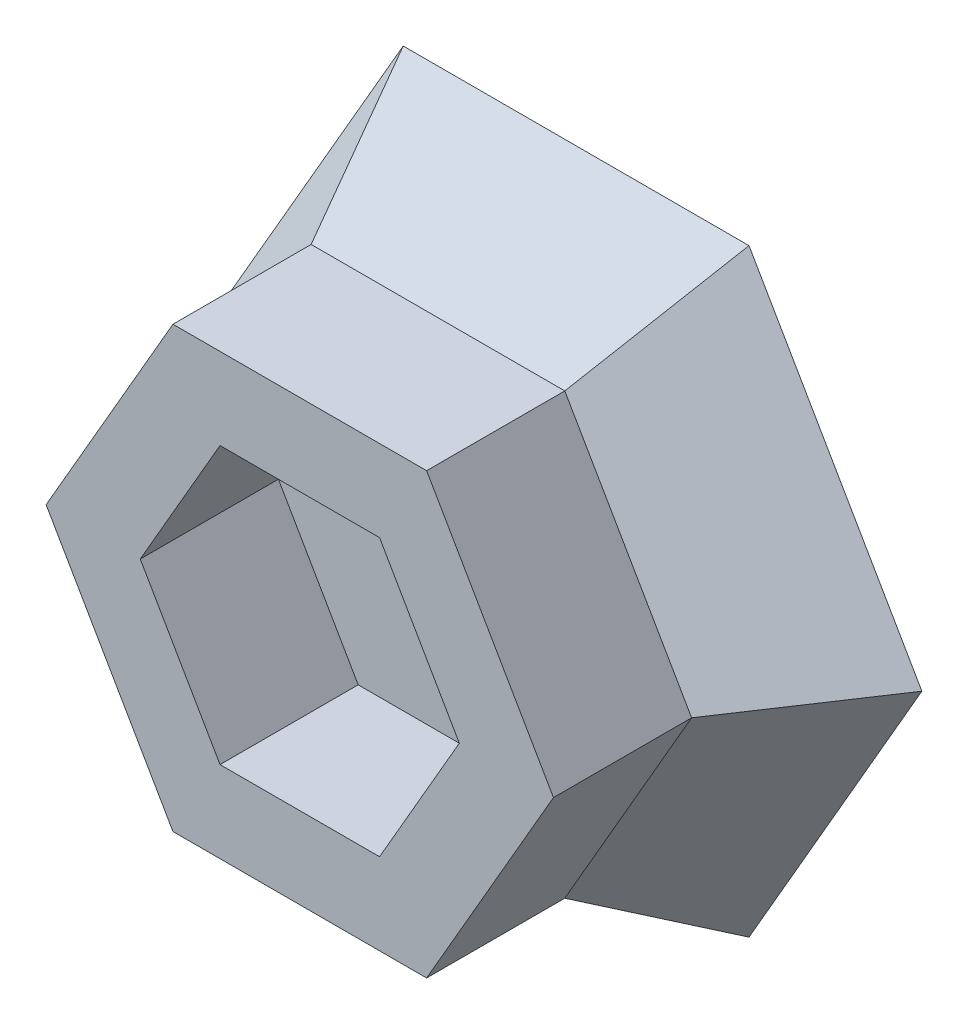
SolidWorks part; units mm, degrees
ref_plane "Front Plane" through (0, 0, 0) normal (0, 0, 1) x (1, 0, 0)
ref_plane "Top Plane" through (0, 0, 0) normal (0, 1, 0) x (1, 0, 0)
ref_plane "Right Plane" through (0, 0, 0) normal (1, 0, 0) x (0, 0, -1)
sketch "Sketch1" plane through (0, 0, 0) normal (0, 0, 1) x (1, 0, 0)
  line L1 (5.7735, 0) -> (2.8868, 5)
  line L2 (2.8868, 5) -> (-2.8868, 5)
  line L3 (-2.8868, 5) -> (-5.7735, 0)
  line L4 (-5.7735, 0) -> (-2.8868, -5)
  line L5 (-2.8868, -5) -> (2.8868, -5)
  line L6 (2.8868, -5) -> (5.7735, 0)
  line L7 (9.1799, 0) -> (4.5899, 7.95)
  line L8 (4.5899, 7.95) -> (-4.5899, 7.95)
  line L9 (-4.5899, 7.95) -> (-9.1799, 0)
  line L10 (-9.1799, 0) -> (-4.5899, -7.95)
  line L11 (-4.5899, -7.95) -> (4.5899, -7.95)
  line L12 (4.5899, -7.95) -> (9.1799, 0)
  circle A0 centre (0, 0) radius 5 construction
  circle A2 centre (0, 0) radius 7.95 construction
  dimension "D1" = 10
  dimension "D3" = 15.9
extrude "Boss-Extrude1" add sketch "Sketch1" along normal blind 5
extrude "Boss-Extrude2" add sketch "Sketch1<2>" against normal blind 5 draft 30 contours L5 L6 L1 L2 L3 L4 | L6 L5 L4 L3 L2 L1 region at (0, 0, 0) region at (6.6746, -3.8536, 0) draft outward yes
sketch "Sketch1<2>" plane through (0, 0, 0) normal (0, 0, 1) x (1, 0, 0) same geometry as "Sketch1"
